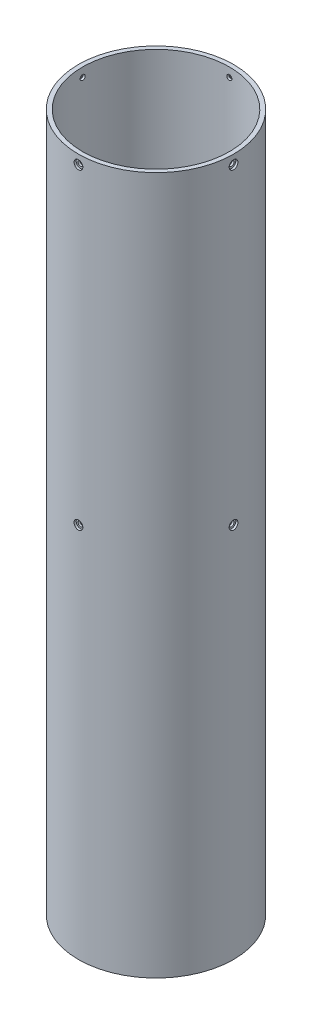
SolidWorks part; units mm, degrees
material "Hexcel AS4C (3000 Filaments)"
ref_plane "Front Plane" through (0, 0, 0) normal (0, 0, 1) x (1, 0, 0)
ref_plane "Top Plane" through (0, 0, 0) normal (0, 1, 0) x (1, 0, 0)
ref_plane "Right Plane" through (0, 0, 0) normal (1, 0, 0) x (0, 0, -1)
sketch "Sketch1" plane through (0, 0, 0) normal (0, 1, 0) x (1, 0, 0)
  circle A0 centre (0, 0) radius 50.8
  dimension "D1" = 101.6
extrude "Body Extrusion" add sketch "Sketch1" along normal blind 482.6 thin thin type one direction wall 2.921
ref_plane "Plane1" through (0, 0, 53.721) normal (0, 0, 1) x (1, 0, 0)
sketch "Sketch2" plane through (0, 0, 53.721) normal (0, 0, 1) x (1, 0, 0)
  line L0 (0, 482.6) -> (0, 0) construction
  line L1 (53.721, 482.6) -> (-53.721, 482.6) construction
  line L3 (50.8, 482.6) -> (-50.8, 482.6) construction
  circle A0 centre (0, 476.25) radius 1.7526
  dimension "D1" = 3.5052
  dimension "D2" = 6.35
extrude "Upper Bulkhead Holes" cut sketch "Sketch2" against normal up to next
pattern_circular "Upper Bulkhead Hole Pattern" count 4 over 360 about axis through (0, 482.6, 0) along (0, -1, 0) of "Upper Bulkhead Holes"
sketch "Sketch3" plane through (0, 0, 53.721) normal (0, 0, 1) x (1, 0, 0)
  line L0 (0, 482.6) -> (0, 0) construction
  line L1 (53.721, 482.6) -> (-53.721, 482.6) construction
  line L2 (50.8, 482.6) -> (-50.8, 482.6) construction
  circle A0 centre (0, 260.35) radius 1.7526
  dimension "D1" = 3.5052
  dimension "D2" = 260.35
  dimension "D3" = 222.25
extrude "Lower Bulkhead Holes" cut sketch "Sketch3" against normal up to next
pattern_circular "Lower Bulkhead Hole Pattern" count 4 over 360 about axis through (0, 482.6, 0) along (0, -1, 0) of "Lower Bulkhead Holes" reverse direction yes
sketch "Sketch4" plane through (0, 0, 53.721) normal (0, 0, 1) x (1, 0, 0)
  line L0 (0, 482.6) -> (0, 0) construction
  line L1 (50.8, 482.6) -> (-50.8, 482.6) construction
  line L2 (-50.8, 0) -> (50.8, 0) construction
  circle A0 centre (0, 476.25) radius 3.0226
  circle A1 centre (0, 260.35) radius 3.0226
  circle A2 centre (0, 260.35) radius 1.7526 construction
  circle A3 centre (0, 476.25) radius 1.7526 construction
  dimension "D1" = 1.27
  dimension "D2" = 1.27
extrude "Countersink" cut sketch "Sketch4" against normal blind 1.524
pattern_circular "Countersink Pattern" count 4 over 360 about axis through (0, 482.6, 0) along (0, -1, 0) of "Countersink"
equation "\"D2@Sketch4\"=\"D1@Sketch4\""
